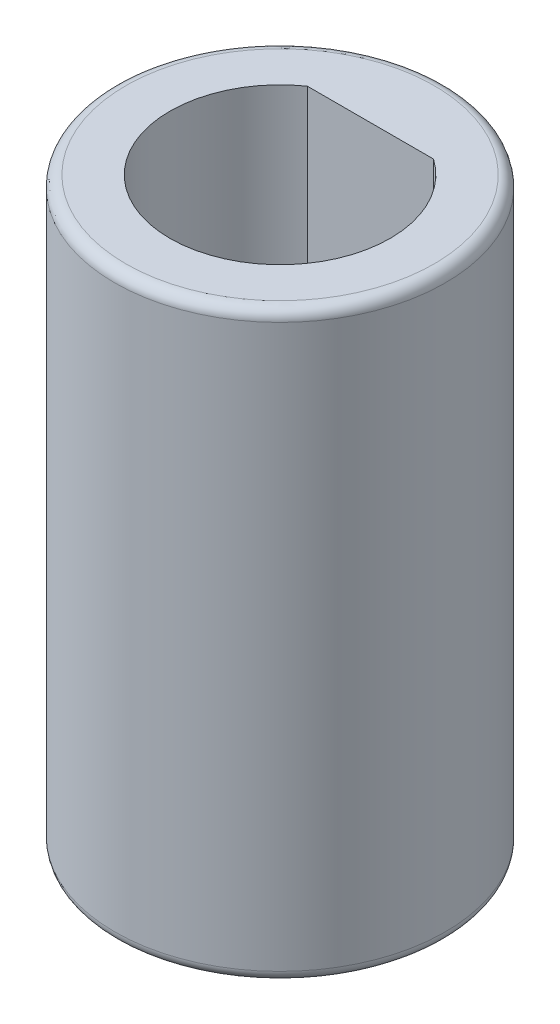
SolidWorks part; units mm, degrees
ref_plane "前视基准面" through (0, 0, 0) normal (0, 0, 1) x (1, 0, 0)
ref_plane "上视基准面" through (0, 0, 0) normal (0, 1, 0) x (1, 0, 0)
ref_plane "右视基准面" through (0, 0, 0) normal (1, 0, 0) x (0, 0, -1)
sketch "草图1" plane through (0, 0, 0) normal (0, 1, 0) x (1, 0, 0)
  circle A0 centre (0, 0) radius 1.5
extrude "凸台-拉伸1" add sketch "草图1" along normal blind 5.3
sketch "草图2" plane through (0, 5.3, 0) normal (0, 1, 0) x (1, 0, 0)
  line L0 (-0.5724, 0.82) -> (0.5724, 0.82)
  arc A0 (-0.5724, 0.82) -> (0.5724, 0.82) centre (0, 0) ccw
  dimension "D1" = 0.82
extrude "切除-拉伸1" cut sketch "草图2" against normal up to next
sketch "草图3" plane through (0, 0, 0) normal (0, -1, 0) x (-1, 0, 0)
  circle A0 centre (0, 0) radius 1.1
extrude "切除-拉伸2" cut sketch "草图3" against normal blind 1.75
sketch "草图4" plane through (0, 0, 0) normal (0, 0, 1) x (1, 0, 0)
  circle A0 centre (0, 4) radius 1
hole_wizard "M1.6 螺纹孔1" [suppressed] positions "草图7" profile "草图9" tap size "M1.6" standard "ISO"
sketch "草图7" plane through (0, 0, 0) normal (0, 0, 1) x (1, 0, 0)
  point P0 (0, 4)
sketch "草图9" plane through (0, 4, 0) normal (1, 0, 0) x (0, -1, 0)
  line L0 (0, 0) -> (0, 1.5)
  line L1 (0, 1.5) -> (0.625, 1.5)
  line L2 (0.625, 1.5) -> (0.625, 0)
  line L5 (0.625, 0) -> (0, 0)
  line L11 (0, -6.35) -> (0, 107.95) construction
  dimension "通孔螺纹孔钻头直径" = 1.25
  dimension "通孔螺纹孔钻头深度" = 1.5
cosmetic thread "孔螺蚊线1" [suppressed] parameters "D2"=1.6
fillet "圆角1" radius 0.1 3 edges at (0, 0, -1.1) (0, 0, 1.5) (0, 5.3, 1.5)
chamfer "倒角1" distance 0.1 angle 45 2 edges at (0, 1.75, -0.82) (0, 1.75, 1)
